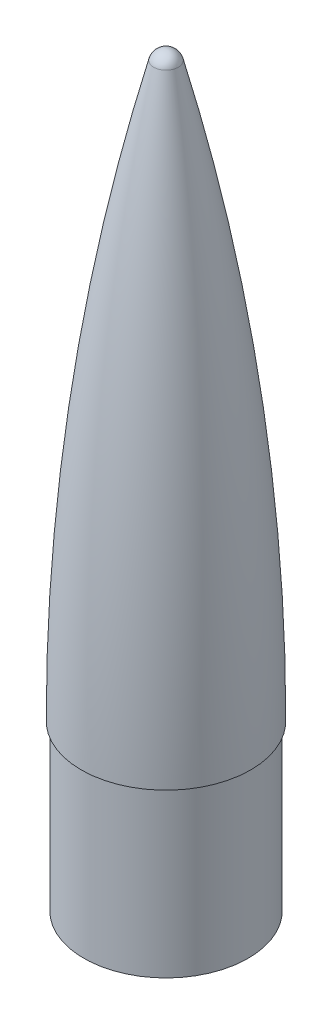
SolidWorks part; units mm, degrees
ref_plane "Front Plane" through (0, 0, 0) normal (0, 0, 1) x (1, 0, 0)
ref_plane "Top Plane" through (0, 0, 0) normal (0, 1, 0) x (1, 0, 0)
ref_plane "Right Plane" through (0, 0, 0) normal (1, 0, 0) x (0, 0, -1)
sketch "Sketch1" plane through (0, 0, 0) normal (0, 0, 1) x (1, 0, 0)
  line L0 (0, 0) -> (32.5, 0)
  line L1 (0, 0) -> (0, 295)
  line L2 (33.5, 65) -> (32.5, 65)
  line L3 (32.5, 65) -> (32.5, 0)
  line L4 (33.5, 65) -> (33.5, 0) construction
  line L5 (33.5, 0) -> (32.5, 0) construction
  line L6 (0, 295) -> (-5, 295) construction
  arc A0 (0, 295) -> (4.8421, 291.2467) centre (0, 290) cw
  arc A1 (4.8421, 291.2467) -> (33.5, 65) centre (-873.9079, 65) cw
  point P8 (5.6818, 290.9281)
  dimension "D6" = 5
  dimension "D1" = 295
  dimension "D2" = 1
  dimension "D3" = 65
  dimension "D4" = 32.5
  dimension "D5" = 5
revolve "Revolve1" add sketch "Sketch1" angle 360 about L1
